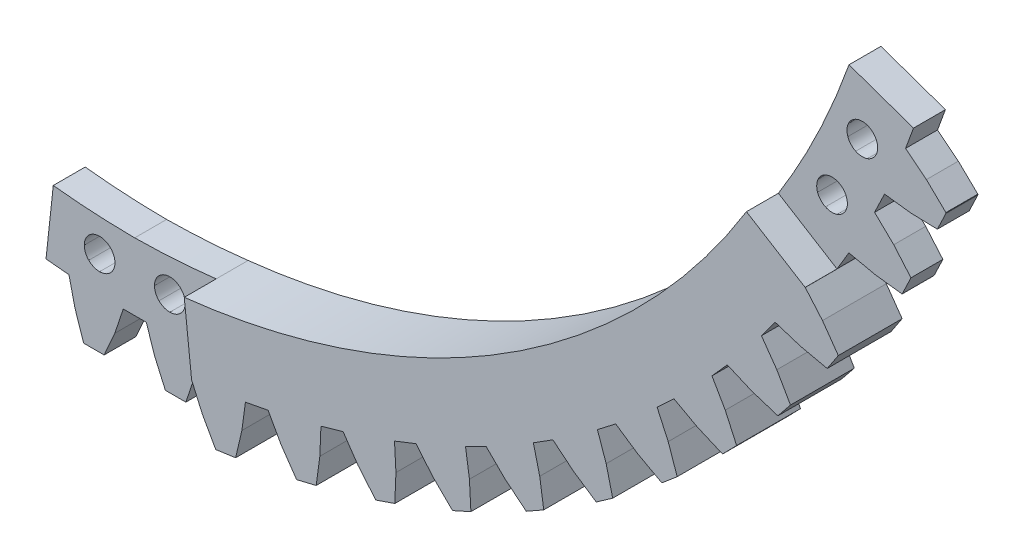
SolidWorks part; units mm, degrees
ref_plane "Front Plane" through (0, 0, 0) normal (0, 0, 1) x (1, 0, 0)
ref_plane "Top Plane" through (0, 0, 0) normal (0, 1, 0) x (1, 0, 0)
ref_plane "Right Plane" through (0, 0, 0) normal (1, 0, 0) x (0, 0, -1)
sketch "Model" plane through (0, 0, 0) normal (0, 0, 1) x (1, 0, 0)
  line L0 (97.6897, 59.494) -> (93.6504, 60.9123)
  line L1 (54.4501, 25.204) -> (53.9899, 29.4544)
  line L521 (46.9691, 21.814) -> (45.6858, 21.814)
  line L522 (45.6858, 21.814) -> (46.9431, 21.7551)
  line L523 (46.9431, 21.7551) -> (46.9691, 21.814)
  line L524 (52.0788, 21.814) -> (50.8066, 21.814)
  line L525 (50.8066, 21.814) -> (50.8325, 21.7551)
  line L526 (50.8325, 21.7551) -> (52.0788, 21.814)
  line L527 (97.6869, 59.4863) -> (97.6897, 59.494)
  line L528 (93.6476, 60.9051) -> (97.6869, 59.4863)
  line L529 (99.7292, 55.8979) -> (99.7319, 55.9045)
  line L530 (99.7319, 55.9045) -> (99.7176, 55.9183)
  line L531 (99.7176, 55.9183) -> (99.7292, 55.8979)
  line L532 (99.1818, 54.7453) -> (99.243, 54.7436)
  line L533 (99.243, 54.7436) -> (99.7066, 55.845)
  line L534 (99.7066, 55.845) -> (99.1818, 54.7453)
  line L535 (96.9885, 50.1542) -> (97.5679, 51.2341)
  line L536 (97.5679, 51.2341) -> (97.5271, 51.2815)
  line L537 (97.5271, 51.2815) -> (96.9885, 50.1542)
  line L538 (53.9899, 29.4544) -> (54.4501, 25.204)
  line L539 (54.4501, 25.204) -> (55.1237, 23.6788)
  line L540 (55.1237, 23.6788) -> (55.9627, 22.1789)
  line L541 (55.9627, 22.1789) -> (57.2095, 22.3553)
  line L542 (57.2095, 22.3553) -> (57.5987, 24.0294)
  line L543 (57.5987, 24.0294) -> (57.8219, 25.6819)
  line L544 (57.8219, 25.6819) -> (59.2413, 25.9515)
  line L545 (59.2413, 25.9515) -> (60.0544, 24.4957)
  line L546 (60.0544, 24.4957) -> (61.0306, 23.0807)
  line L547 (61.0306, 23.0807) -> (62.2548, 23.3734)
  line L548 (62.2548, 23.3734) -> (62.4858, 25.0761)
  line L549 (62.4858, 25.0761) -> (62.5536, 26.7425)
  line L550 (62.5536, 26.7425) -> (63.941, 27.1437)
  line L551 (63.941, 27.1437) -> (64.8874, 25.7707)
  line L552 (64.8874, 25.7707) -> (65.9915, 24.4533)
  line L553 (65.9915, 24.4533) -> (67.1832, 24.8595)
  line L554 (67.1832, 24.8595) -> (67.2538, 26.5765)
  line L555 (67.2538, 26.5765) -> (67.165, 28.2418)
  line L556 (67.165, 28.2418) -> (68.5089, 28.7709)
  line L557 (68.5089, 28.7709) -> (69.5794, 27.4927)
  line L558 (69.5794, 27.4927) -> (70.802, 26.2844)
  line L559 (70.802, 26.2844) -> (71.9507, 26.8003)
  line L560 (71.9507, 26.8003) -> (71.8597, 28.5163)
  line L561 (71.8597, 28.5163) -> (71.6155, 30.1661)
  line L562 (71.6155, 30.1661) -> (72.9043, 30.8187)
  line L563 (72.9043, 30.8187) -> (74.0899, 29.6463)
  line L564 (74.0899, 29.6463) -> (75.42, 28.5582)
  line L565 (75.42, 28.5582) -> (76.5153, 29.1794)
  line L566 (76.5153, 29.1794) -> (76.2645, 30.8793)
  line L567 (76.2645, 30.8793) -> (75.8665, 32.4988)
  line L568 (75.8665, 32.4988) -> (77.0886, 33.2694)
  line L569 (77.0886, 33.2694) -> (78.379, 32.2127)
  line L570 (78.379, 32.2127) -> (79.8049, 31.2542)
  line L571 (79.8049, 31.2542) -> (80.8374, 31.9751)
  line L572 (80.8374, 31.9751) -> (80.4284, 33.6442)
  line L573 (80.4284, 33.6442) -> (79.8805, 35.2196)
  line L574 (79.8805, 35.2196) -> (81.0248, 36.101)
  line L575 (81.0248, 36.101) -> (82.4083, 35.17)
  line L576 (82.4083, 35.17) -> (83.9181, 34.3487)
  line L577 (83.9181, 34.3487) -> (84.8783, 35.1634)
  line L578 (84.8783, 35.1634) -> (84.315, 36.7867)
  line L579 (84.315, 36.7867) -> (83.6221, 38.3036)
  line L580 (83.6221, 38.3036) -> (84.6788, 39.2887)
  line L581 (84.6788, 39.2887) -> (86.1434, 38.4911)
  line L582 (86.1434, 38.4911) -> (87.7232, 37.8153)
  line L583 (87.7232, 37.8153) -> (88.6029, 38.716)
  line L584 (88.6029, 38.716) -> (87.8902, 40.2798)
  line L585 (87.8902, 40.2798) -> (87.0584, 41.725)
  line L586 (87.0584, 41.725) -> (88.0181, 42.8043)
  line L587 (88.0181, 42.8043) -> (89.551, 42.1478)
  line L588 (89.551, 42.1478) -> (91.187, 41.6225)
  line L589 (91.187, 41.6225) -> (91.9785, 42.602)
  line L590 (91.9785, 42.602) -> (91.1225, 44.092)
  line L591 (91.1225, 44.092) -> (90.159, 45.4529)
  line L592 (90.159, 45.4529) -> (91.0134, 46.6176)
  line L593 (91.0134, 46.6176) -> (92.6009, 46.1072)
  line L594 (92.6009, 46.1072) -> (94.2793, 45.7379)
  line L595 (94.2793, 45.7379) -> (94.9755, 46.7868)
  line L596 (94.9755, 46.7868) -> (93.9839, 48.1897)
  line L597 (93.9839, 48.1897) -> (92.9024, 49.4481)
  line L598 (92.9024, 49.4481) -> (92.8952, 49.447)
  line L599 (92.8952, 49.447) -> (89.2203, 51.7164)
  line L600 (89.2203, 51.7164) -> (92.8952, 49.447)
  line L601 (92.8952, 49.447) -> (92.9024, 49.4481)
  line L602 (92.9024, 49.4481) -> (92.8969, 49.4547)
  line L603 (92.8969, 49.4547) -> (93.6388, 50.6944)
  line L604 (93.6388, 50.6944) -> (95.2671, 50.335)
  line L605 (95.2671, 50.335) -> (96.9725, 50.1245)
  line L606 (96.9725, 50.1245) -> (96.9885, 50.1542)
  line L607 (96.9885, 50.1542) -> (97.5271, 51.2815)
  line L608 (97.5271, 51.2815) -> (96.4489, 52.5382)
  line L609 (96.4489, 52.5382) -> (95.2483, 53.6958)
  line L610 (95.2483, 53.6958) -> (95.8707, 54.9994)
  line L611 (95.8707, 54.9994) -> (97.5254, 54.7938)
  line L612 (97.5254, 54.7938) -> (99.1818, 54.7453)
  line L613 (99.1818, 54.7453) -> (99.7066, 55.845)
  line L614 (99.7066, 55.845) -> (99.7292, 55.8979)
  line L615 (99.7292, 55.8979) -> (99.7176, 55.9183)
  line L616 (99.7176, 55.9183) -> (98.4956, 57.0979)
  line L617 (98.4956, 57.0979) -> (97.1919, 58.138)
  line L618 (97.1919, 58.138) -> (97.6869, 59.4863)
  line L619 (97.6869, 59.4863) -> (93.6476, 60.9051)
  line L620 (43.7814, 29.4208) -> (43.3255, 25.2035)
  line L621 (43.3255, 25.2035) -> (44.7636, 25.0684)
  line L622 (44.7636, 25.0684) -> (45.1412, 23.444)
  line L623 (45.1412, 23.444) -> (45.6858, 21.814)
  line L624 (45.6858, 21.814) -> (46.9691, 21.814)
  line L625 (46.9691, 21.814) -> (47.6382, 23.3271)
  line L626 (47.6382, 23.3271) -> (48.1657, 24.9091)
  line L627 (48.1657, 24.9091) -> (49.6099, 24.9091)
  line L628 (49.6099, 24.9091) -> (50.138, 23.3271)
  line L629 (50.138, 23.3271) -> (50.8066, 21.814)
  line L630 (50.8066, 21.814) -> (52.0788, 21.814)
  line L631 (52.0788, 21.814) -> (52.0904, 21.8146)
  line L632 (52.0904, 21.8146) -> (52.635, 23.4445)
  line L633 (52.635, 23.4445) -> (53.012, 25.069)
  line L634 (53.012, 25.069) -> (54.4501, 25.204)
  spline S0 degree 3 poles (93.6504, 60.9123) (93.6495, 60.9099) (93.6485, 60.9075) (93.6476, 60.9051) knots 0 0 0 0 1 1 1 1
  spline S1 degree 3 poles (89.2203, 51.7164) (81.5328, 39.2652) (68.5355, 31.0523) (53.9899, 29.4544) knots 0 0 0 0 1 1 1 1
  spline S2 degree 3 poles (93.6476, 60.9051) (92.5059, 57.6922) (91.0216, 54.6115) (89.2203, 51.7164) knots 0 0 0 0 1 1 1 1
  spline S3 degree 3 poles (53.9899, 29.4544) (52.2954, 29.2542) (50.5913, 29.1455) (48.8851, 29.1287) knots 0 0 0 0 1 1 1 1
  spline S4 degree 3 poles (48.8851, 29.1287) (47.1798, 29.1344) (45.4761, 29.2319) (43.7814, 29.4208) knots 0 0 0 0 1 1 1 1
  spline S5 degree 3 poles (47.6463, 27.1541) (47.6463, 26.8992) (47.5451, 26.6546) (47.3648, 26.4743) knots 0 0 0 0 1 1 1 1
  spline S6 degree 3 poles (47.3648, 26.4743) (47.1845, 26.294) (46.9399, 26.1927) (46.6849, 26.1927) knots 0 0 0 0 1 1 1 1
  spline S7 degree 3 poles (46.6849, 26.1927) (46.43, 26.1927) (46.1854, 26.294) (46.0051, 26.4743) knots 0 0 0 0 1 1 1 1
  spline S8 degree 3 poles (46.0051, 26.4743) (45.8248, 26.6546) (45.7236, 26.8992) (45.7236, 27.1541) knots 0 0 0 0 1 1 1 1
  spline S9 degree 3 poles (45.7236, 27.1541) (45.7236, 27.4091) (45.8248, 27.6537) (46.0051, 27.834) knots 0 0 0 0 1 1 1 1
  spline S10 degree 3 poles (46.0051, 27.834) (46.1854, 28.0143) (46.43, 28.1155) (46.6849, 28.1155) knots 0 0 0 0 1 1 1 1
  spline S11 degree 3 poles (46.6849, 28.1155) (46.9399, 28.1155) (47.1845, 28.0143) (47.3648, 27.834) knots 0 0 0 0 1 1 1 1
  spline S12 degree 3 poles (47.3648, 27.834) (47.5451, 27.6537) (47.6463, 27.4091) (47.6463, 27.1541) knots 0 0 0 0 1 1 1 1
  spline S13 degree 3 poles (52.0462, 27.1541) (52.0462, 26.8992) (51.945, 26.6546) (51.7647, 26.4743) knots 0 0 0 0 1 1 1 1
  spline S14 degree 3 poles (51.7647, 26.4743) (51.5844, 26.294) (51.3398, 26.1927) (51.0849, 26.1927) knots 0 0 0 0 1 1 1 1
  spline S15 degree 3 poles (51.0849, 26.1927) (50.8299, 26.1927) (50.5853, 26.294) (50.405, 26.4743) knots 0 0 0 0 1 1 1 1
  spline S16 degree 3 poles (50.405, 26.4743) (50.2247, 26.6546) (50.1235, 26.8992) (50.1235, 27.1541) knots 0 0 0 0 1 1 1 1
  spline S17 degree 3 poles (50.1235, 27.1541) (50.1235, 27.4091) (50.2247, 27.6537) (50.405, 27.834) knots 0 0 0 0 1 1 1 1
  spline S18 degree 3 poles (50.405, 27.834) (50.5853, 28.0143) (50.8299, 28.1155) (51.0849, 28.1155) knots 0 0 0 0 1 1 1 1
  spline S19 degree 3 poles (51.0849, 28.1155) (51.3398, 28.1155) (51.5844, 28.0143) (51.7647, 27.834) knots 0 0 0 0 1 1 1 1
  spline S20 degree 3 poles (51.7647, 27.834) (51.945, 27.6537) (52.0462, 27.4091) (52.0462, 27.1541) knots 0 0 0 0 1 1 1 1
  spline S21 degree 3 poles (92.997, 54.1866) (93.2271, 54.0768) (93.4041, 53.88) (93.4891, 53.6396) knots 0 0 0 0 1 1 1 1
  spline S22 degree 3 poles (93.4891, 53.6396) (93.5741, 53.3992) (93.5601, 53.1349) (93.4502, 52.9048) knots 0 0 0 0 1 1 1 1
  spline S23 degree 3 poles (93.4502, 52.9048) (93.3403, 52.6747) (93.1435, 52.4977) (92.9031, 52.4127) knots 0 0 0 0 1 1 1 1
  spline S24 degree 3 poles (92.9031, 52.4127) (92.6627, 52.3277) (92.3984, 52.3417) (92.1683, 52.4516) knots 0 0 0 0 1 1 1 1
  spline S25 degree 3 poles (92.1683, 52.4516) (91.9382, 52.5615) (91.7612, 52.7583) (91.6762, 52.9987) knots 0 0 0 0 1 1 1 1
  spline S26 degree 3 poles (91.6762, 52.9987) (91.5913, 53.2391) (91.6052, 53.5034) (91.7151, 53.7335) knots 0 0 0 0 1 1 1 1
  spline S27 degree 3 poles (91.7151, 53.7335) (91.825, 53.9635) (92.0218, 54.1405) (92.2622, 54.2255) knots 0 0 0 0 1 1 1 1
  spline S28 degree 3 poles (92.2622, 54.2255) (92.5026, 54.3105) (92.7669, 54.2965) (92.997, 54.1866) knots 0 0 0 0 1 1 1 1
  spline S29 degree 3 poles (94.8933, 58.1569) (95.1234, 58.047) (95.3004, 57.8503) (95.3854, 57.6099) knots 0 0 0 0 1 1 1 1
  spline S30 degree 3 poles (95.3854, 57.6099) (95.4704, 57.3695) (95.4564, 57.1052) (95.3465, 56.8751) knots 0 0 0 0 1 1 1 1
  spline S31 degree 3 poles (95.3465, 56.8751) (95.2366, 56.645) (95.0398, 56.468) (94.7994, 56.383) knots 0 0 0 0 1 1 1 1
  spline S32 degree 3 poles (94.7994, 56.383) (94.559, 56.298) (94.2947, 56.312) (94.0646, 56.4219) knots 0 0 0 0 1 1 1 1
  spline S33 degree 3 poles (94.0646, 56.4219) (93.8345, 56.5318) (93.6575, 56.7286) (93.5725, 56.969) knots 0 0 0 0 1 1 1 1
  spline S34 degree 3 poles (93.5725, 56.969) (93.4875, 57.2094) (93.5015, 57.4737) (93.6114, 57.7038) knots 0 0 0 0 1 1 1 1
  spline S35 degree 3 poles (93.6114, 57.7038) (93.7213, 57.9338) (93.9181, 58.1108) (94.1585, 58.1958) knots 0 0 0 0 1 1 1 1
  spline S36 degree 3 poles (94.1585, 58.1958) (94.3989, 58.2808) (94.6632, 58.2668) (94.8933, 58.1569) knots 0 0 0 0 1 1 1 1
extrude "Boss-Extrude1" add sketch "Model" along normal blind 4 contours L599 S1 L1 L539 L540 L541 L542 L543 L544 L545 L546 L547 L548 L549 L550 L551 L552 L553 L554 L555 L556 L557 L558 L559 L560 L561 L562 L563 L564 L565 L566 L567 L568 L569 L570 L571 L572 L573 L574 L575 L576 L577 L578 L579 L580 L581 L582 L583 L584 L585 L586 region at (74.9575, 35.3333, 0)
extrude "Boss-Extrude2" add sketch "Model<3>" along normal blind 2 contours S3 S4 L620 L621 L622 L623 L521 L625 L626 L627 L628 L629 L524 L631 L632 L633 L634 L1 S11 S12 S5 S6 S7 S8 S9 S10 S19 S20 S13 S14 S15 S16 S17 S18 | L528 S2 L599 L598 L602 L603 L604 L605 L606 L537 L608 L609 L610 L611 L612 L534 L614 L531 L616 L617 L618 S27 S28 S21 S22 S23 S24 S25 S26 S35 S36 S29 S30 S31 S32 S33 S34 region at (94.4354, 54.8721, 0) region at (48.8934, 26.1163, 0)
sketch "Model<3>" plane through (0, 0, 0) normal (0, 0, 1) x (1, 0, 0) same geometry as "Model"
